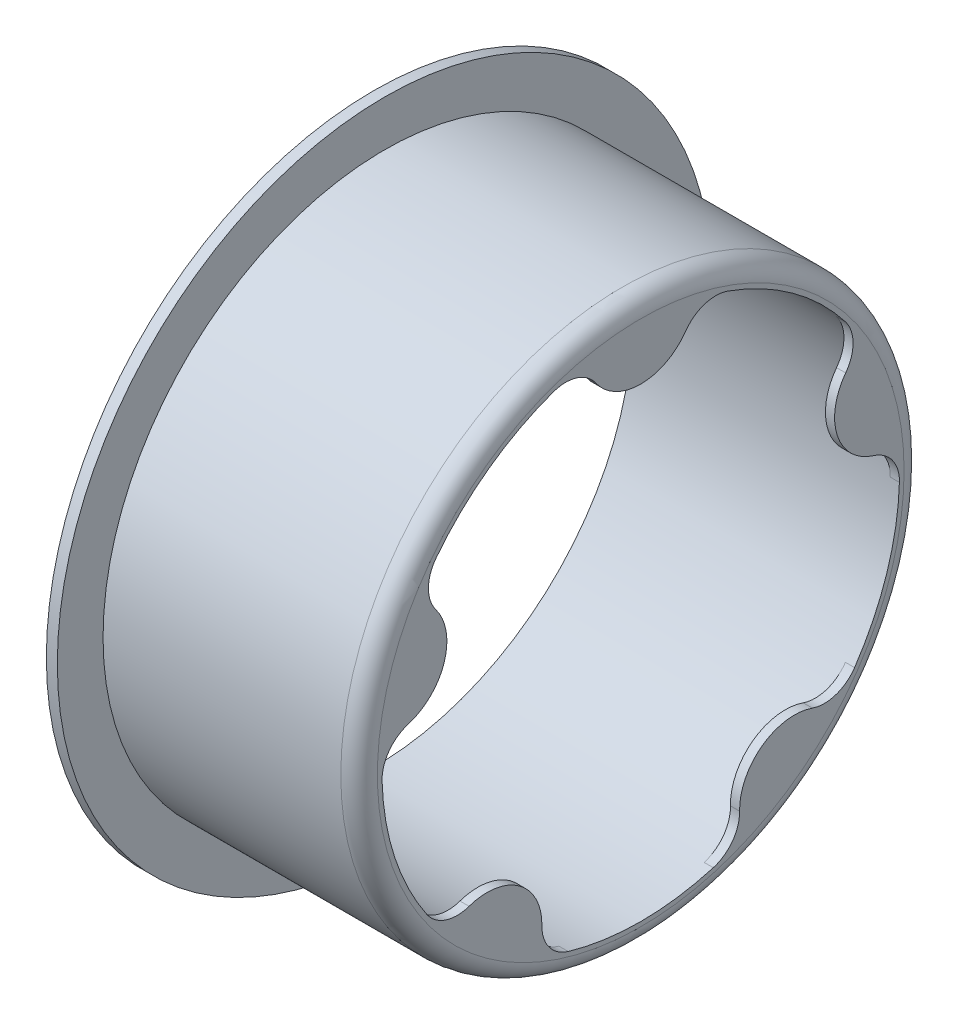
SolidWorks part; units mm, degrees
ref_plane "前视基准面" through (0, 0, 0) normal (0, 0, 1) x (1, 0, 0)
ref_plane "上视基准面" through (0, 0, 0) normal (0, 1, 0) x (1, 0, 0)
ref_plane "右视基准面" through (0, 0, 0) normal (1, 0, 0) x (0, 0, -1)
sketch "草图2" plane through (0, 0, 0) normal (0, 1, 0) x (1, 0, 0)
  line L0 (-68.5531, 0) -> (68.5531, 0) construction
  line L1 (0, 57.8778) -> (0, -48.6174) construction
  line L2 (-7.6, 14.15) -> (-7.6, 17.9)
  line L3 (-7.6, 17.9) -> (-7, 17.9)
  line L4 (-7, 17.9) -> (-7, 15.4)
  line L5 (-7, 15.4) -> (7, 15.4)
  line L6 (7, 17.9) -> (7, 15.4)
  line L7 (-7.6, 14.15) -> (7.6, 14.15)
  line L8 (7.6, 17.9) -> (7, 17.9)
  line L9 (7.6, 14.15) -> (7.6, 17.9)
  point P7 (0, 14.15)
  point P13 (0, 15.4)
  dimension "D1" = 14.15
  dimension "D2" = 14
  dimension "D3" = 0.6
  dimension "D4" = 1.25
  dimension "D5" = 2.5
revolve "旋转1" add sketch "草图2" angle 360 about L0
sketch "草图3" plane through (7.6, 0, 0) normal (1, 0, 0) x (0, 0, -1)
  circle A0 centre (0, 0) radius 19
  dimension "D1" = 38
extrude "切除-拉伸1" cut sketch "草图3" against normal up to surface (0.6 mm away) up to face at (7, 0, 15.4)
sketch "草图4" plane through (7, 0, 0) normal (1, 0, 0) x (0, 0, -1)
  line L0 (0, 21.059) -> (0, 17) construction
  line L1 (0, 14.3) -> (0, -17.1858) construction
  arc A0 (-12.3789, 7.1591) -> (-14.2228, 1.4843) centre (0, 0) ccw
  arc A1 (-2.9834, 13.9853) -> (2.9834, 13.9853) centre (0, 14.3) ccw
  arc A2 (12.3789, 7.1591) -> (14.2228, 1.4843) centre (13.6001, 4.4189) ccw
  arc A3 (10.634, -9.5607) -> (5.8067, -13.068) centre (8.4053, -11.5689) ccw
  arc A4 (-5.8067, -13.068) -> (-10.634, -9.5607) centre (-8.4053, -11.5689) ccw
  arc A5 (-14.2228, 1.4843) -> (-12.3789, 7.1591) centre (-13.6001, 4.4189) ccw
  arc A6 (2.9834, 13.9853) -> (-2.9834, 13.9853) centre (0, 0) ccw
  arc A7 (-10.634, -9.5607) -> (-5.8067, -13.068) centre (0, 0) ccw
  arc A8 (5.8067, -13.068) -> (10.634, -9.5607) centre (0, 0) ccw
  arc A9 (14.2228, 1.4843) -> (12.3789, 7.1591) centre (0, 0) ccw
  point P24 (0, 0)
  dimension "D1" = 6
  dimension "D3" = 14.3
  dimension "D2" = 5
extrude "凸台-拉伸1" add sketch "草图4" against normal blind 0.5
fillet "圆角1" radius 2 10 edges at (6.75, 7.0944, -12.243) (6.75, 1.4567, -14.0748) (6.75, -9.4515, -10.5305) (6.75, -12.9358, -5.7348) (6.75, -9.4515, 10.5305) (6.75, -12.9358, 5.7348) (6.75, 1.4567, 14.0748) (6.75, 7.0944, 12.243) (6.75, 13.8361, -2.9639) (6.75, 13.8361, 2.9639)
fillet "圆角2" radius 1 1 edges at (7, 0, -15.4)
